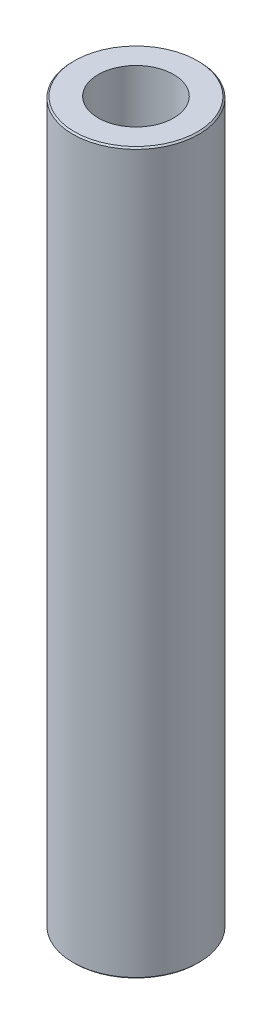
SolidWorks part; units mm, degrees
ref_plane "Front Plane" through (0, 0, 0) normal (0, 0, 1) x (1, 0, 0)
ref_plane "Top Plane" through (0, 0, 0) normal (0, 1, 0) x (1, 0, 0)
ref_plane "Right Plane" through (0, 0, 0) normal (1, 0, 0) x (0, 0, -1)
sketch "Sketch1" plane through (0, 0, 0) normal (0, 1, 0) x (1, 0, 0)
  circle A0 centre (0, 0) radius 52.5
  dimension "SHAFT_OD" = 105
extrude "Boss-Extrude1" add sketch "Sketch1" along normal blind 600
sketch "Sketch2" plane through (0, 0, 0) normal (0, 1, 0) x (1, 0, 0)
  circle A0 centre (0, 0) radius 31.4271
  dimension "BORE_D" = 62.8542
extrude "Cut-Extrude1" cut sketch "Sketch2" along normal through all
chamfer "Chamfer1" distance 1.2191 angle 45 2 edges at (0, 600, 52.5) (0, 0, 52.5)
